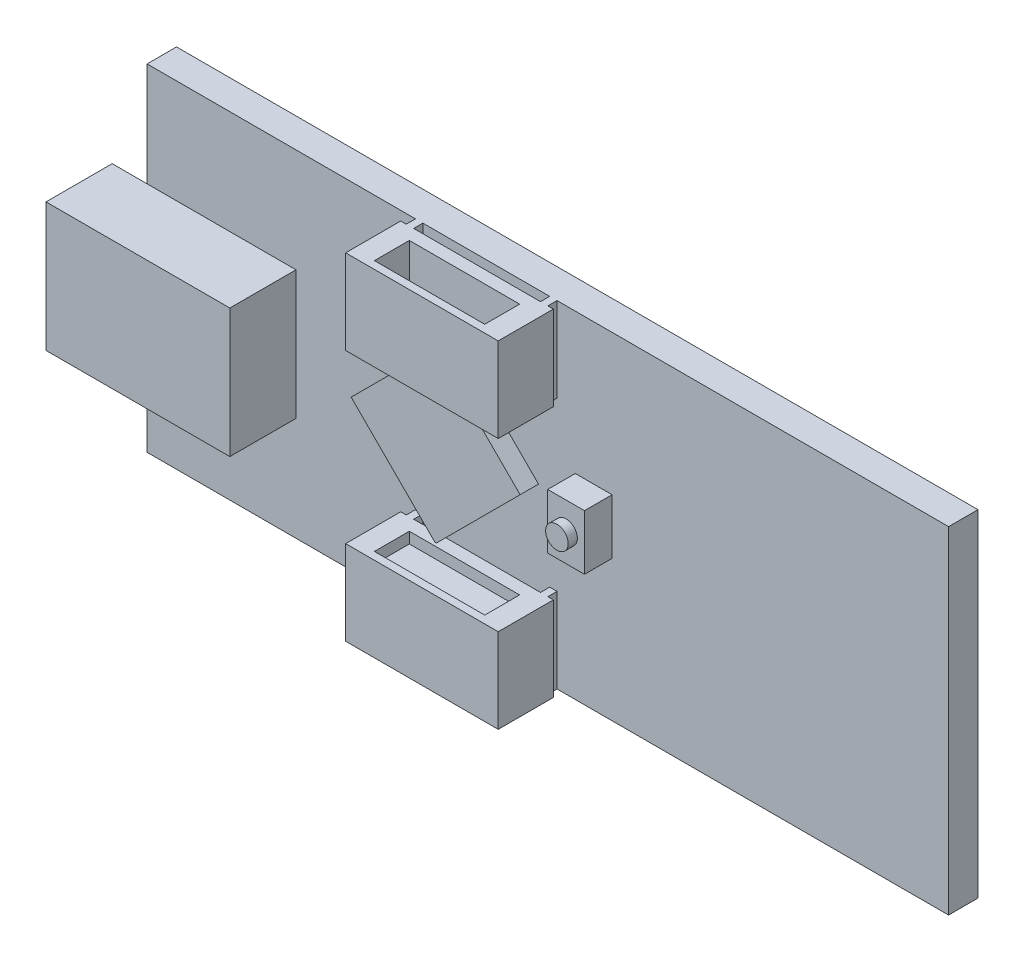
SolidWorks part; units mm, degrees
note: The reader was unsure of these and kept them because the rebuilt part matched: shared geometry of "Sketch6<3>".
ref_plane "Front Plane" through (0, 0, 0) normal (0, 0, 1) x (1, 0, 0)
ref_plane "Top Plane" through (0, 0, 0) normal (0, 1, 0) x (1, 0, 0)
ref_plane "Right Plane" through (0, 0, 0) normal (1, 0, 0) x (0, 0, -1)
sketch "Sketch1" plane through (0, 0, 0) normal (0, 0, 1) x (1, 0, 0)
  line L0 (-21.8, 9.15) -> (21.8, -9.15) construction
  line L1 (-21.8, -9.15) -> (21.8, -9.15)
  line L2 (-21.8, -9.15) -> (-21.8, 9.15)
  line L3 (-21.8, 9.15) -> (21.8, 9.15)
  line L4 (21.8, -9.15) -> (21.8, 9.15)
  point P5 (0, 0)
  dimension "D1" = 43.6
  dimension "D2" = 18.3
extrude "Boss-Extrude1" add sketch "Sketch1" along normal blind 1.6
sketch "Sketch2" plane through (-21.8, 0, 0) normal (-1, 0, 0) x (0, 0, 1)
  line L0 (1.6, 9.15) -> (1.6, -9.15) construction
  line L1 (1.6, 3.5) -> (5.2, 3.5)
  line L2 (1.6, 3.5) -> (1.6, -3.5)
  line L3 (1.6, -3.5) -> (5.2, -3.5)
  line L4 (5.2, 3.5) -> (5.2, -3.5)
  line L5 (0, 0) -> (4.7935, 0) construction
  line L6 (0, 9.15) -> (0, -9.15) construction
  point P7 (5.2, 0)
  dimension "D1" = 7
  dimension "D2" = 3.6
extrude "USB Connector" add sketch "Sketch2" against normal blind 10 from offset 1.9
sketch "Sketch3" plane through (0, 0, 1.6) normal (0, 0, 1) x (1, 0, 0)
  line L0 (-9.7, 0) -> (-5.1038, 4.5962)
  line L1 (-9.7, 0) -> (-5.1038, -4.5962)
  line L2 (-5.1038, 4.5962) -> (-0.5076, 0)
  line L3 (-5.1038, -4.5962) -> (-0.5076, 0)
  line L4 (0.88, 0) -> (-0.88, 0) construction
  line L5 (-13.7, 3.5) -> (-13.7, -3.5) construction
  dimension "D1" = 6.5
  dimension "D2" = 4
extrude "MicroProcessor" add sketch "Sketch3" along normal blind 1
sketch "Sketch4" plane through (0, 0, 1.6) normal (0, 0, 1) x (1, 0, 0)
  line L0 (0.88, 0) -> (-0.88, 0) construction
  line L1 (1.4924, 1.5) -> (3.4924, 1.5)
  line L2 (1.4924, 1.5) -> (1.4924, -1.5)
  line L3 (1.4924, -1.5) -> (3.4924, -1.5)
  line L4 (3.4924, 1.5) -> (3.4924, -1.5)
  point P4 (1.4924, 0)
  dimension "D1" = 3
  dimension "D2" = 2
  dimension "D3" = 2
extrude "Button Base" add sketch "Sketch4" along normal blind 1.5
sketch "Sketch5" plane through (0, 0, 3.1) normal (0, 0, 1) x (1, 0, 0)
  line L0 (1.4924, 1.5) -> (3.4924, -1.5) construction
  circle A0 centre (2.4924, 0) radius 0.6136
extrude "Button" add sketch "Sketch5" along normal blind 0.5
sketch "Sketch6" plane through (0, -9.15, 0) normal (0, -1, 0) x (1, 0, 0)
  line L0 (-21.8, 1.6) -> (21.8, 1.6) construction
  line L1 (0.8, 2.1) -> (-7.5, 2.1)
  line L2 (0.8, 2.1) -> (0.8, 5.1)
  line L3 (0.8, 5.1) -> (-7.5, 5.1)
  line L4 (-7.5, 2.1) -> (-7.5, 5.1)
  line L5 (21.8, 1.6) -> (21.8, 0) construction
  line L6 (-7.5, 5.1) -> (0.8, 2.1) construction
  line L7 (-6.35, 4.6843) -> (-0.35, 4.6843)
  line L8 (-6.35, 4.6843) -> (-6.35, 2.7843)
  line L9 (-6.35, 2.7843) -> (-0.35, 2.7843)
  line L10 (-0.35, 4.6843) -> (-0.35, 2.7843)
  line L11 (-3.35, 3.6) -> (-3.35, 6.6639) construction
  line L12 (-7.2, 2.1) -> (-6.8, 2.1)
  line L13 (-7.2, 2.1) -> (-7.2, 1.6)
  line L14 (-7.2, 1.6) -> (-6.8, 1.6)
  line L15 (-6.8, 2.1) -> (-6.8, 1.6)
  line L16 (0.1, 2.1) -> (0.5, 2.1)
  line L17 (0.1, 2.1) -> (0.1, 1.6)
  line L18 (0.1, 1.6) -> (0.5, 1.6)
  line L19 (0.5, 2.1) -> (0.5, 1.6)
  point P22 (-3.35, 4.6843)
  line M3 (21.8, 1.6) -> (-21.8, 1.6)
  dimension "D1" = 8.3
  dimension "D2" = 3
  dimension "D3" = 0.5
  dimension "D4" = 21
  dimension "D5" = 6
  dimension "D6" = 1.9
  dimension "D8" = 0.3
  dimension "D9" = 0.4
  dimension "D10" = 0.4
  dimension "D11" = 0.3
extrude "JST x 6" add sketch "Sketch6" against normal blind 4.6 separate body contours L15 L1 L13 M3 | L19 L1 L17 M3 | L3 L6 L7 L10 L2 | L6 L4 L1 L10 L9 L8
extrude "Boss-Extrude8" add sketch "Sketch6<3>" along normal blind 0.8 from offset 4 contours L7 L6 L10 | L6 L8 L9 L10
sketch "Sketch6<3>" plane through (0, -9.15, 0) normal (0, -1, 0) x (1, 0, 0) same geometry as "Sketch6"
mirror "Mirror5" about plane through (0, 0, 0) normal (0, 1, 0) of "Boss-Extrude8", "JST x 6"
